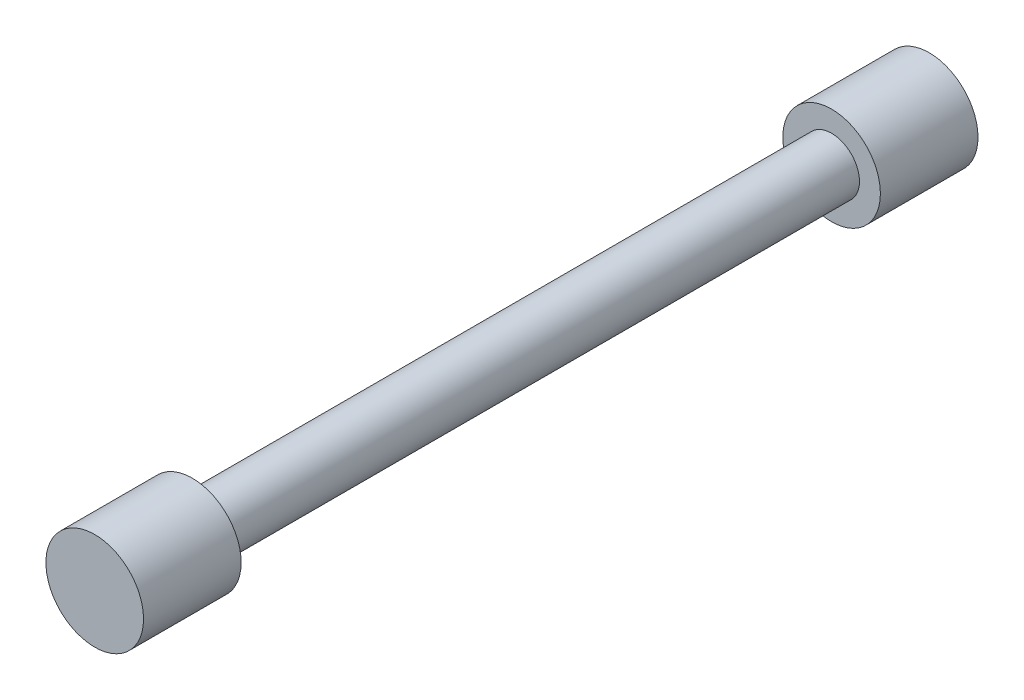
SolidWorks part; units mm, degrees
ref_plane "Front Plane" through (0, 0, 0) normal (0, 0, 1) x (1, 0, 0)
ref_plane "Top Plane" through (0, 0, 0) normal (0, 1, 0) x (1, 0, 0)
ref_plane "Right Plane" through (0, 0, 0) normal (1, 0, 0) x (0, 0, -1)
sketch "SK_Rod" plane through (0, 0, 0) normal (0, 1, 0) x (1, 0, 0)
  line L0 (0, -10) -> (0, 115.6835) construction
  line L1 (0, -7) -> (7, -7)
  line L2 (7, -7) -> (7, 7)
  line L3 (7, 7) -> (4, 7)
  line L4 (4, 7) -> (4, 98.6835)
  line L5 (4, 98.6835) -> (7, 98.6835)
  line L6 (7, 98.6835) -> (7, 112.6835)
  line L7 (7, 112.6835) -> (0, 112.6835)
  line L8 (0, 112.6835) -> (0, -7)
  dimension "P1" = 10
  dimension "P2" = 115.6835
  dimension "P3" = 7
  dimension "P4" = 7
  dimension "P5" = 7
  dimension "P6" = 7
  dimension "P7" = 7
  dimension "P8" = 4
  dimension "P9" = 7
  dimension "P10" = 4
  dimension "P11" = 98.6835
  dimension "P12" = 7
  dimension "P13" = 98.6835
  dimension "P14" = 7
  dimension "P15" = 112.6835
  dimension "P16" = 112.6835
revolve "Rod_Body" add sketch "SK_Rod" angle 360 about L0
equation "\"Rod_length\" = 105.683"
